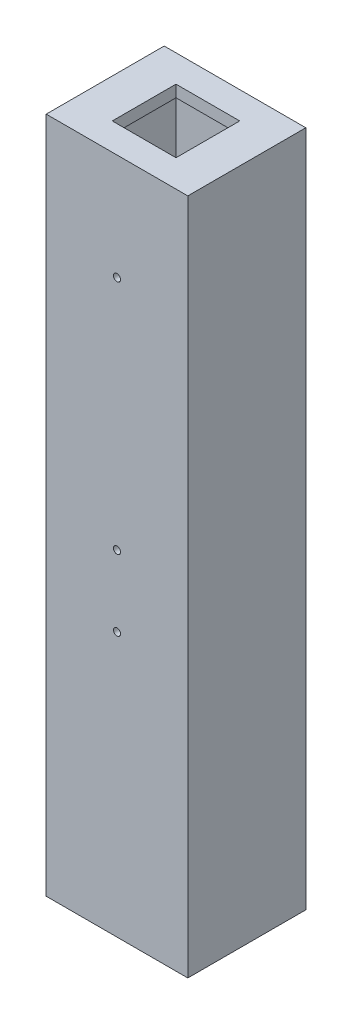
SolidWorks part; units mm, degrees
ref_plane "前视基准面" through (0, 0, 0) normal (0, 0, 1) x (1, 0, 0)
ref_plane "上视基准面" through (0, 0, 0) normal (0, 1, 0) x (1, 0, 0)
ref_plane "右视基准面" through (0, 0, 0) normal (1, 0, 0) x (0, 0, -1)
other "Configuration Table"
sketch "草图1" plane through (0, 0, 0) normal (0, 1, 0) x (1, 0, 0)
  line L1 (-3.1, 3.1) -> (3.1, 3.1)
  line L2 (-3.1, 3.1) -> (-3.1, -3.1)
  line L3 (-3.1, -3.1) -> (3.1, -3.1)
  line L4 (3.1, 3.1) -> (3.1, -3.1)
  line L5 (-3.1, 3.1) -> (3.1, -3.1) construction
  line L6 (-3.1, -3.1) -> (3.1, 3.1) construction
  line L7 (-6, 5) -> (6, 5)
  line L8 (-6, 5) -> (-6, -5)
  line L9 (-6, -5) -> (6, -5)
  line L10 (6, 5) -> (6, -5)
  line L11 (-6, 5) -> (6, -5) construction
  line L12 (-6, -5) -> (6, 5) construction
  line L13 (-2.7, -2.7) -> (2.7, -2.7)
  line L14 (-2.7, -2.7) -> (-2.7, 2.7)
  line L15 (-2.7, 2.7) -> (2.7, 2.7)
  line L16 (2.7, -2.7) -> (2.7, 2.7)
  line L17 (-2.7, -2.7) -> (2.7, 2.7) construction
  line L18 (-2.7, 2.7) -> (2.7, -2.7) construction
  point P0 (0, 0)
  point P5 (0, 0)
  point P13 (0, 0)
  dimension "D1" = 6.2
  dimension "D2" = 10
  dimension "D3" = 5.4
  dimension "D4" = 12
extrude "凸台-拉伸1" add sketch "草图1" along normal blind 54 contours L10 L7 L8 L9 L1 L4 L3 L2 region at (0, 0, -4.8438)
extrude "凸台-拉伸2" add sketch "草图1<3>" against normal blind 1 from surface contours L10 L7 L8 L9 L1 L4 L3 L2 | L4 L1 L2 L3 L16 L13 L14 L15 region at (0, 0, -3.0123) region at (0, 0, -4.8438) starting at face at (0, 54, 0)
sketch "草图1<3>" plane through (0, 0, 0) normal (0, 1, 0) x (1, 0, 0) same geometry as "草图1"
sketch "草图3" plane through (0, 0, 0) normal (0, -1, 0) x (1, 0, 0)
  line L1 (-3.6, 3.6) -> (3.6, 3.6)
  line L2 (-3.6, 3.6) -> (-3.6, -3.6)
  line L3 (-3.6, -3.6) -> (3.6, -3.6)
  line L4 (3.6, 3.6) -> (3.6, -3.6)
  line L5 (-3.6, 3.6) -> (3.6, -3.6) construction
  line L6 (-3.6, -3.6) -> (3.6, 3.6) construction
  line L7 (-6, 5) -> (6, 5)
  line L8 (-6, 5) -> (-6, -5)
  line L9 (-6, -5) -> (6, -5)
  line L10 (6, 5) -> (6, -5)
  point P0 (0, 0)
  dimension "D1" = 7.2
extrude "凸台-拉伸3" add sketch "草图3" along normal blind 3.4 contours L8 L9 L10 L7 | L2 L3 L4 L1
sketch "草图2" plane through (0, -3.4, 0) normal (0, -1, 0) x (1, 0, 0)
  line L0 (-6, -5) -> (-6, 5) construction
  line L8 (-6, 5) -> (6, 5) construction
  line L9 (-6, -5) -> (6, -5) construction
  line L10 (6, -5) -> (6, 5) construction
  circle A0 centre (-4.5, 3.5) radius 0.3
  circle A1 centre (4.5, -3.5) radius 0.3
  circle A2 centre (4.5, 3.5) radius 0.3
  circle A3 centre (-4.5, -3.5) radius 0.3
  point P0 (0, 0)
  dimension "D2" = 0.6
  dimension "D3" = 1.5
  dimension "D4" = 1.5
  dimension "D5" = 1.5
  dimension "D6" = 1.5
extrude "切除-拉伸1" cut sketch "草图2" against normal blind 2 contours A0 | A2 | A3 | A1
sketch "草图7" plane through (0, 0, -5) normal (0, 0, -1) x (-1, 0, 0)
  line L0 (0, 54) -> (0, -3.4)
  line L1 (6, 54) -> (-6, 54) construction
  line L2 (6, -3.4) -> (-6, -3.4) construction
  circle A0 centre (0, 19) radius 0.3
  circle A1 centre (0, 25) radius 0.3
  circle A2 centre (0, 45) radius 0.3
  point P6 (0, 0)
  dimension "D1" = 0.6
  dimension "D2" = 22.4
  dimension "D3" = 6
  dimension "D4" = 20
extrude "切除-拉伸2" cut sketch "草图7" against normal through all contours A0 | A1 | A2
